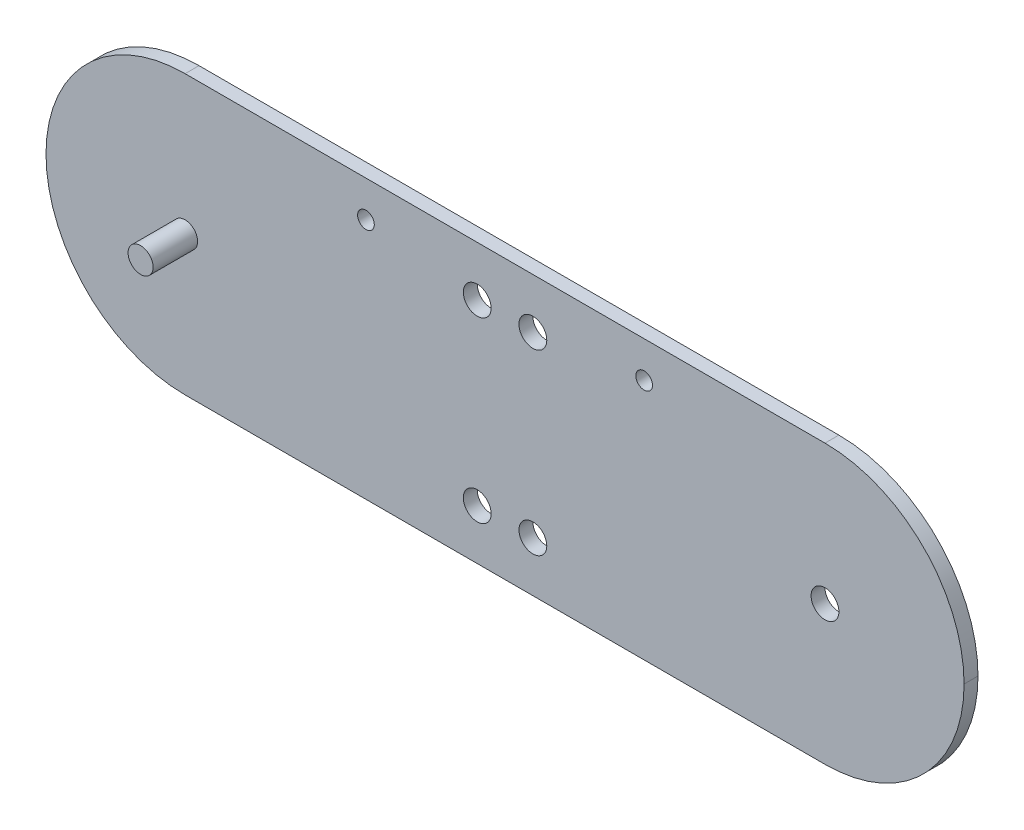
SolidWorks part; units mm, degrees
ref_plane "Front Plane" through (0, 0, 0) normal (0, 0, 1) x (1, 0, 0)
ref_plane "Top Plane" through (0, 0, 0) normal (0, 1, 0) x (1, 0, 0)
ref_plane "Right Plane" through (0, 0, 0) normal (1, 0, 0) x (0, 0, -1)
sketch "Sketch1" plane through (0, 0, 0) normal (0, 0, 1) x (1, 0, 0)
  line L1 (82.5, 25) -> (-82.5, 25)
  line L2 (82.5, 25) -> (82.5, -25)
  line L3 (82.5, -25) -> (-82.5, -25)
  line L4 (-82.5, 25) -> (-82.5, -25)
  line L5 (82.5, 25) -> (-82.5, -25) construction
  line L6 (82.5, -25) -> (-82.5, 25) construction
  point P0 (0, 0)
  dimension "D1" = 50
  dimension "D2" = 165
extrude "Boss-Extrude1" add sketch "Sketch1" along normal blind 2.5
fillet "Fillet1" radius 25 4 edges at (-82.5, -25, 1.25) (-82.5, 25, 1.25) (82.5, -25, 1.25) (82.5, 25, 1.25)
sketch "Sketch2" plane through (0, 0, 2.5) normal (0, 0, 1) x (1, 0, 0)
  line L0 (0, 0) -> (0, 16)
  line L1 (0, 16) -> (-5, 16)
  line L2 (-5, 16) -> (5, 16)
  circle A0 centre (-5, 16) radius 2.5
  circle A1 centre (5, 16) radius 2.5
  dimension "D4" = 5
  dimension "D5" = 5
  dimension "D1" = 16
  dimension "D2" = 5
  dimension "D3" = 10
extrude "Cut-Extrude1" cut sketch "Sketch2" against normal blind 2.5 contours A0 | A1 region at (-7.4293, 16, 2.5) region at (5, 18.4293, 2.5)
mirror "Mirror1" about plane through (0, 0, 0) normal (0, 1, 0) of "Cut-Extrude1"
sketch "Sketch3" plane through (0, 0, 0) normal (0, 0, -1) x (-1, 0, 0)
  line L0 (0, 0) -> (-57.5, 0)
  circle A0 centre (-57.5, 0) radius 2.5
  dimension "D2" = 5
  dimension "D1" = 57.5
extrude "Cut-Extrude2" cut sketch "Sketch3" against normal blind 2.5 contours A0 region at (59.9293, 0, 0)
sketch "Sketch4" plane through (0, 0, 2.5) normal (0, 0, 1) x (1, 0, 0)
  line L0 (0, 0) -> (-57.5, 0)
  circle A0 centre (-57.5, 0) radius 2.25
  dimension "D2" = 4.5
  dimension "D1" = 57.5
extrude "Boss-Extrude2" add sketch "Sketch4" along normal blind 8 contours A0 region at (-59.6864, 0, 2.5)
sketch "Sketch6" plane through (0, 0, 0) normal (0, 0, -1) x (-1, 0, 0)
  line L0 (-29.6676, 0) -> (33.0547, 0) construction
  line L2 (37.0467, 18.5) -> (-49.2106, 18.5) construction
  line L3 (-57.5, 25) -> (57.5, 25) construction
  circle A2 centre (-25, 18.5) radius 1.5
  circle A4 centre (25, 18.5) radius 1.5
  dimension "D1" = 3
  dimension "D3" = 3
  dimension "D4" = 50
  dimension "D2" = 6.5
extrude "Cut-Extrude4" cut sketch "Sketch6" against normal through all
